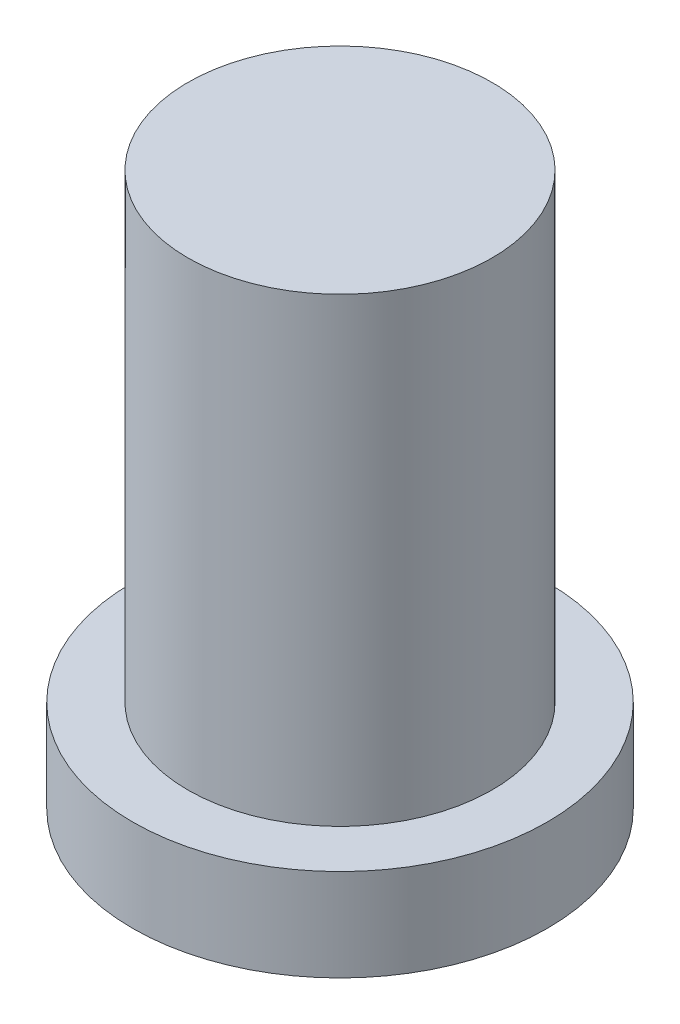
SolidWorks part; units mm, degrees
ref_plane "Front Plane" through (0, 0, 0) normal (0, 0, 1) x (1, 0, 0)
ref_plane "Top Plane" through (0, 0, 0) normal (0, 1, 0) x (1, 0, 0)
ref_plane "Right Plane" through (0, 0, 0) normal (1, 0, 0) x (0, 0, -1)
sketch "Sketch1" plane through (0, 0, 0) normal (0, 1, 0) x (1, 0, 0)
  circle A0 centre (0, 0) radius 4.5
  circle A1 centre (0, 0) radius 3.3
  dimension "D1" = 9
  dimension "D2" = 6.6
extrude "Boss-Extrude1" add sketch "Sketch1" along normal blind 12 contours A1
extrude "Boss-Extrude2" add sketch "Sketch1<3>" along normal blind 2
sketch "Sketch1<3>" plane through (0, 0, 0) normal (0, 1, 0) x (1, 0, 0) same geometry as "Sketch1"
